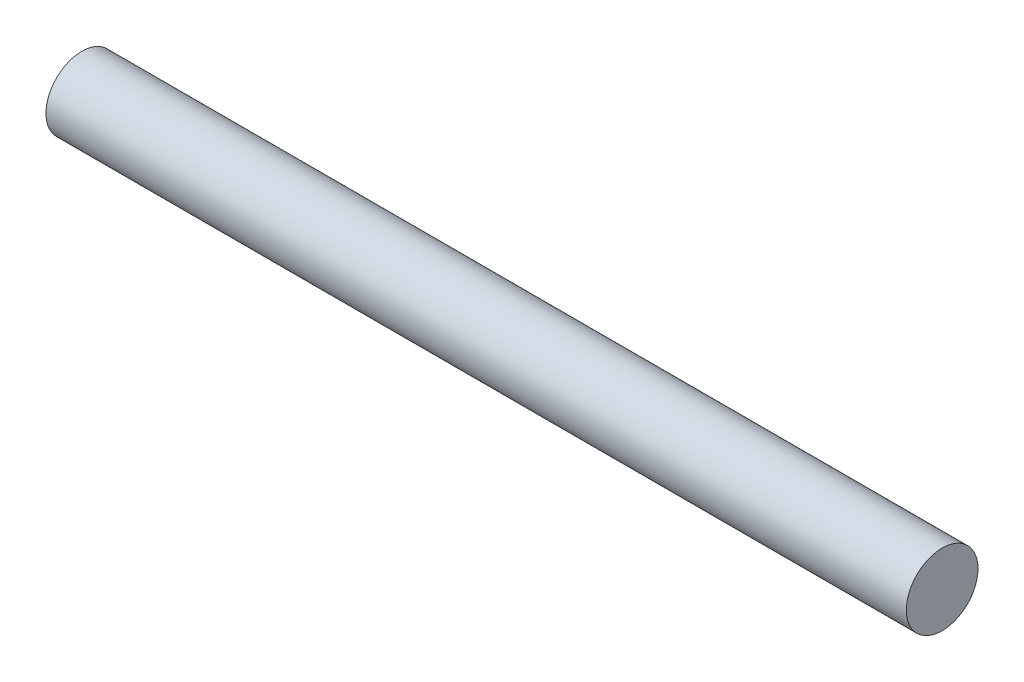
SolidWorks part; units mm, degrees
ref_plane "Front Plane" through (0, 0, 0) normal (0, 0, 1) x (1, 0, 0)
ref_plane "Top Plane" through (0, 0, 0) normal (0, 1, 0) x (1, 0, 0)
ref_plane "Right Plane" through (0, 0, 0) normal (1, 0, 0) x (0, 0, -1)
sketch "Sketch1" plane through (0, 0, 0) normal (1, 0, 0) x (0, 0, -1)
  circle A0 centre (0, 0) radius 2.5
  dimension "D1" = 5
extrude "Boss-Extrude1" add sketch "Sketch1" along normal blind 30 and the other way blind 30
